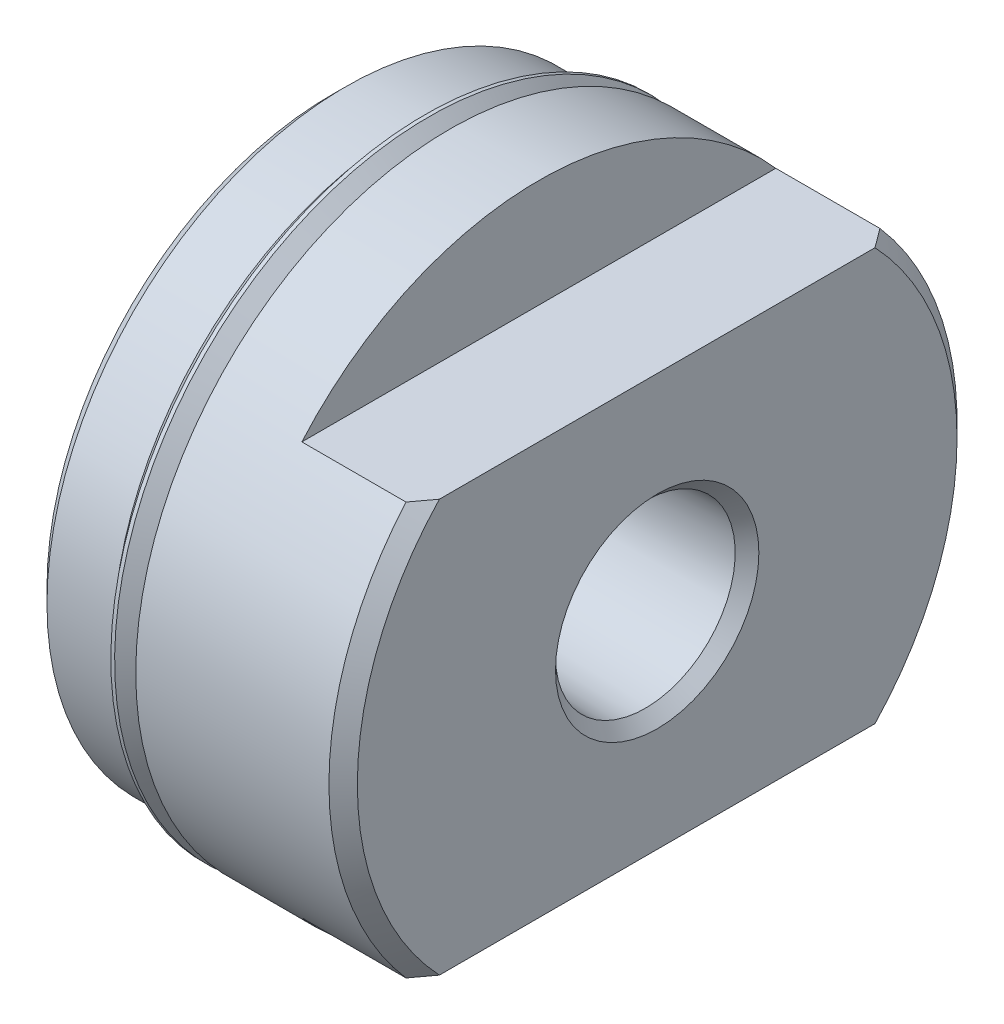
SolidWorks part; units mm, degrees
ref_plane "Front Plane" through (0, 0, 0) normal (0, 0, 1) x (1, 0, 0)
ref_plane "Top Plane" through (0, 0, 0) normal (0, 1, 0) x (1, 0, 0)
ref_plane "Right Plane" through (0, 0, 0) normal (1, 0, 0) x (0, 0, -1)
sketch "Sketch1" plane through (0, 0, 0) normal (0, 0, 1) x (1, 0, 0)
  line L0 (0, 0) -> (0, 15.2591)
  line L1 (0, 15.2591) -> (0.762, 16.021)
  line L2 (0.762, 16.021) -> (4.318, 16.021)
  line L3 (4.318, 16.021) -> (5.334, 15.0051)
  line L4 (5.334, 15.0051) -> (6.35, 15.0051)
  line L5 (6.35, 15.0051) -> (6.35, 16.8466)
  line L6 (6.35, 16.8466) -> (16.7132, 16.8466)
  line L7 (16.7132, 16.8466) -> (17.4752, 16.0846)
  line L8 (17.4752, 16.0846) -> (17.4752, 0)
  line L9 (17.4752, 0) -> (0, 0)
  line L10 (17.4752, 0) -> (0, 0) construction
revolve "Revolve1" add sketch "Sketch1" angle 360 about L10 reverse direction yes
sketch "Sketch2" plane through (0, 0, 0) normal (0, 0, 1) x (1, 0, 0)
  line L0 (0, 0) -> (0, 4.3688)
  line L1 (0, 4.3688) -> (2.3989, 4.3688)
  line L2 (2.3989, 4.3688) -> (16.8402, 4.8197)
  line L3 (16.8402, 4.8197) -> (17.4752, 5.4547)
  line L4 (17.4752, 5.4547) -> (17.4752, 0)
  line L5 (17.4752, 0) -> (0, 0)
  line L6 (17.4752, 0) -> (0, 0) construction
revolve "Cut-Revolve1" cut sketch "Sketch2" angle 360 about L6 reverse direction yes
cosmetic thread "Cosmetic Thread1" parameters "D1"=6.9342, "D2"=10.287
ref_plane "Plane1" through (17.4752, 0, 0) normal (1, 0, 0) x (0, 0, -1)
sketch "Sketch3" plane through (17.4752, 0, 0) normal (1, 0, 0) x (0, 0, -1)
  line L0 (-67.3862, 33.6931) -> (-67.3862, -33.6931)
  line L1 (-67.3862, -33.6931) -> (67.3862, -33.6931)
  line L2 (67.3862, -33.6931) -> (67.3862, 33.6931)
  line L3 (67.3862, 33.6931) -> (-67.3862, 33.6931)
  line L4 (-33.6931, 11.0554) -> (-33.6931, -11.0554)
  line L5 (-33.6931, -11.0554) -> (33.6931, -11.0554)
  line L6 (33.6931, -11.0554) -> (33.6931, 11.0554)
  line L7 (33.6931, 11.0554) -> (-33.6931, 11.0554)
extrude "Cut-Extrude1" cut sketch "Sketch3" against normal blind 6.35
sketch "Sketch4" plane through (0, 0, 0) normal (0, 0, 1) x (1, 0, 0)
  line L0 (0, 0) -> (0, 11.1125)
  line L1 (0, 11.1125) -> (7.9248, 11.1125)
  line L2 (7.9248, 11.1125) -> (7.9248, 0)
  line L3 (7.9248, 0) -> (0, 0)
  line L4 (7.9248, 0) -> (0, 0) construction
revolve "Cut-Revolve2" cut sketch "Sketch4" angle 360 about L4 reverse direction yes
ref_plane "Plane2" through (25.4, 0, 0) normal (1, 0, 0) x (0, 0, -1)
ref_plane "Plane3" through (0, 0, 0) normal (0, 0.9998, 0.0175) x (1, 0, 0)
ref_plane "Plane4" through (15.875, 0, 0) normal (1, 0, 0) x (0, 0, -1)
ref_plane "Plane5" through (5.334, 0, 0) normal (1, 0, 0) x (0, 0, -1)
sketch "Sketch5" plane through (0, 0, 0) normal (0, 0, 1) x (1, 0, 0)
  line L0 (5.0135, 16.7624) -> (6.2166, 15.5593)
  line L1 (6.2166, 15.3797) -> (5.842, 15.0051)
  line L2 (5.842, 15.0051) -> (5.334, 15.0051)
  line L3 (5.334, 15.0051) -> (5.334, 14.7511)
  line L4 (5.334, 14.7511) -> (6.35, 14.7511)
  line L5 (6.35, 14.7511) -> (6.35, 15.7133)
  line L6 (6.35, 15.7133) -> (5.2167, 16.8466)
  line L7 (5.2167, 16.8466) -> (5.0135, 16.8466)
  line L8 (5.0135, 16.8466) -> (5.0135, 16.7624)
  line L9 (6.35, 0) -> (5.334, 0) construction
  arc A0 (6.2166, 15.5593) -> (6.2166, 15.3797) centre (6.1268, 15.4695) cw
revolve "Revolve2" add sketch "Sketch5" angle 360 about L9 reverse direction yes
ref_plane "Plane6" through (17.6022, 0, 0) normal (1, 0, 0) x (0, 0, -1)
ref_plane "Plane7" through (0, 0, 0) normal (1, 0, 0) x (0, 0, -1)
ref_plane "Plane8" through (11.1252, 0, 0) normal (1, 0, 0) x (0, 0, -1)
ref_plane "Plane9" through (17.4752, 0, 0) normal (1, 0, 0) x (0, 0, -1)
ref_plane "Plane10" through (0, 0, 0) normal (0, 0, 1) x (1, 0, 0)
ref_plane "Plane11" through (0, 0, 0) normal (0, 1, 0) x (1, 0, 0)
ref_plane "Plane12" through (0, 0, 0) normal (0, 1, 0) x (1, 0, 0)
ref_plane "Plane13" through (25.4, 0, 0) normal (1, 0, 0) x (0, 0, -1)
ref_plane "cut1 XY" through (17.4752, 0, 0) normal (1, 0, 0) x (0, 0, -1)
ref_plane "cut1 XZ" through (0, 11.0554, 0) normal (0, -1, 0) x (-1, 0, 0)
ref_plane "cut1 YZ" through (0, 0, 0) normal (0, 0, -1) x (-1, 0, 0)
ref_axis "cut1 X" through (17.4752, 11.0554, 80.9) along (0, 0, -1)
ref_axis "cut1 Y" through (17.4752, -50, 0) along (0, 1, 0)
ref_axis "cut1 Z" through (80.9, 11.0554, 0) along (-1, 0, 0)
sketch3d "cut1"
  point P0 (17.4752, 11.0554, 0)
ref_plane "cut2 XY" through (17.4752, 0, 0) normal (1, 0, 0) x (0, 0, -1)
ref_plane "cut2 XZ" through (0, -11.0554, 0) normal (0, -1, 0) x (-1, 0, 0)
ref_plane "cut2 YZ" through (0, 0, 0) normal (0, 0, -1) x (-1, 0, 0)
ref_axis "cut2 X" through (17.4752, -11.0554, 80.9) along (0, 0, -1)
ref_axis "cut2 Y" through (17.4752, -50, 0) along (0, 1, 0)
ref_axis "cut2 Z" through (80.9, -11.0554, 0) along (-1, 0, 0)
sketch3d "cut2"
  point P0 (17.4752, -11.0554, 0)
ref_plane "cutf1 XY" through (0, 0, 0) normal (0, 0, 1) x (1, 0, 0)
ref_plane "cutf1 XZ" through (0, 0, 0) normal (0, -1, 0) x (-1, 0, 0)
ref_plane "cutf1 YZ" through (17.4752, 0, 0) normal (1, 0, 0) x (0, 0, -1)
ref_axis "cutf1 X" through (-80.9, 0, 0) along (1, 0, 0)
ref_axis "cutf1 Y" through (17.4752, -50, 0) along (0, 1, 0)
ref_axis "cutf1 Z" through (17.4752, 0, 80.9) along (0, 0, -1)
sketch3d "cutf1"
  point P0 (17.4752, 0, 0)
ref_plane "cutf2 XY" through (0, 0, 0) normal (0, 0, 1) x (1, 0, 0)
ref_plane "cutf2 XZ" through (0, 0, 0) normal (0, -1, 0) x (-1, 0, 0)
ref_plane "cutf2 YZ" through (11.1252, 0, 0) normal (1, 0, 0) x (0, 0, -1)
ref_axis "cutf2 X" through (-80.9, 0, 0) along (1, 0, 0)
ref_axis "cutf2 Y" through (11.1252, -50, 0) along (0, 1, 0)
ref_axis "cutf2 Z" through (11.1252, 0, 80.9) along (0, 0, -1)
sketch3d "cutf2"
  point P0 (11.1252, 0, 0)
ref_plane "lovra XY" through (17.4752, 0, 0) normal (1, 0, 0) x (0, 0, -1)
ref_plane "lovra XZ" through (0, 0, 0) normal (0, 0, -1) x (-1, 0, 0)
ref_plane "lovra YZ" through (0, 0, 0) normal (0, 1, 0) x (1, 0, 0)
ref_axis "lovra X" through (17.4752, -50, 0) along (0, 1, 0)
ref_axis "lovra Y" through (17.4752, 0, -80.9) along (0, 0, 1)
ref_axis "lovra Z" through (80.9, 0, 0) along (-1, 0, 0)
sketch3d "lovra"
  point P0 (17.4752, 0, 0)
ref_plane "lovra1 XY" through (11.1252, 0, 0) normal (1, 0, 0) x (0, 0, -1)
ref_plane "lovra1 XZ" through (0, 0, 0) normal (0, -1, 0) x (-1, 0, 0)
ref_plane "lovra1 YZ" through (0, 0, 0) normal (0, 0, -1) x (-1, 0, 0)
ref_axis "lovra1 X" through (11.1252, 0, 80.9) along (0, 0, -1)
ref_axis "lovra1 Y" through (11.1252, -50, 0) along (0, 1, 0)
ref_axis "lovra1 Z" through (80.9, 0, 0) along (-1, 0, 0)
sketch3d "lovra1"
  point P0 (11.1252, 0, 0)
ref_plane "lovra2 XY" through (11.1252, 0, 0) normal (1, 0, 0) x (0, 0, -1)
ref_plane "lovra2 XZ" through (0, 11.0554, 0) normal (0, -1, 0) x (-1, 0, 0)
ref_plane "lovra2 YZ" through (0, 0, 0) normal (0, 0, -1) x (-1, 0, 0)
ref_axis "lovra2 X" through (11.1252, 11.0554, 80.9) along (0, 0, -1)
ref_axis "lovra2 Y" through (11.1252, -50, 0) along (0, 1, 0)
ref_axis "lovra2 Z" through (80.9, 11.0554, 0) along (-1, 0, 0)
sketch3d "lovra2"
  point P0 (11.1252, 11.0554, 0)
ref_plane "lovra21 XY" through (0, 0, 0) normal (1, 0, 0) x (0, 0, -1)
ref_plane "lovra21 XZ" through (0, 0, 0) normal (0, -1, 0) x (-1, 0, 0)
ref_plane "lovra21 YZ" through (0, 0, 5.2705) normal (0, 0, -1) x (-1, 0, 0)
ref_axis "lovra21 X" through (0, 0, 80.9) along (0, 0, -1)
ref_axis "lovra21 Y" through (0, -50, 5.2705) along (0, 1, 0)
ref_axis "lovra21 Z" through (80.9, 0, 5.2705) along (-1, 0, 0)
sketch3d "lovra21"
  point P0 (0, 0, 5.2705)
ref_plane "lovra22 XY" through (0, 0, 0) normal (1, 0, 0) x (0, 0, -1)
ref_plane "lovra22 XZ" through (0, 0, 0) normal (0, -1, 0) x (-1, 0, 0)
ref_plane "lovra22 YZ" through (0, 0, -5.2705) normal (0, 0, -1) x (-1, 0, 0)
ref_axis "lovra22 X" through (0, 0, 80.9) along (0, 0, -1)
ref_axis "lovra22 Y" through (0, -50, -5.2705) along (0, 1, 0)
ref_axis "lovra22 Z" through (80.9, 0, -5.2705) along (-1, 0, 0)
sketch3d "lovra22"
  point P0 (0, 0, -5.2705)
ref_plane "lovra3 XY" through (11.1252, 0, 0) normal (1, 0, 0) x (0, 0, -1)
ref_plane "lovra3 XZ" through (0, -11.0554, 0) normal (0, -1, 0) x (-1, 0, 0)
ref_plane "lovra3 YZ" through (0, 0, 0) normal (0, 0, -1) x (-1, 0, 0)
ref_axis "lovra3 X" through (11.1252, -11.0554, 80.9) along (0, 0, -1)
ref_axis "lovra3 Y" through (11.1252, -50, 0) along (0, 1, 0)
ref_axis "lovra3 Z" through (80.9, -11.0554, 0) along (-1, 0, 0)
sketch3d "lovra3"
  point P0 (11.1252, -11.0554, 0)
ref_plane "olen XY" through (17.4752, 0, 0) normal (1, 0, 0) x (0, 0, -1)
ref_plane "olen XZ" through (0, 0, 0) normal (0, -1, 0) x (-1, 0, 0)
ref_plane "olen YZ" through (0, 0, 0) normal (0, 0, -1) x (-1, 0, 0)
ref_axis "olen X" through (17.4752, 0, 80.9) along (0, 0, -1)
ref_axis "olen Y" through (17.4752, -50, 0) along (0, 1, 0)
ref_axis "olen Z" through (80.9, 0, 0) along (-1, 0, 0)
sketch3d "olen"
  point P0 (17.4752, 0, 0)
ref_plane "to_mounting_bracket XY" through (25.4, 0, 0) normal (1, 0, 0) x (0, 0, -1)
ref_plane "to_mounting_bracket XZ" through (0, 0, 0) normal (0, -1, 0) x (-1, 0, 0)
ref_plane "to_mounting_bracket YZ" through (0, 0, 0) normal (0, 0, -1) x (-1, 0, 0)
ref_axis "to_mounting_bracket X" through (25.4, 0, 80.9) along (0, 0, -1)
ref_axis "to_mounting_bracket Y" through (25.4, -50, 0) along (0, 1, 0)
ref_axis "to_mounting_bracket Z" through (80.9, 0, 0) along (-1, 0, 0)
sketch3d "to_mounting_bracket"
  point P0 (25.4, 0, 0)
ref_plane "to_nut XY" through (0, 0, 0) normal (1, 0, 0) x (0, 0, -1)
ref_plane "to_nut XZ" through (0, 0, 0) normal (0, -1, 0) x (-1, 0, 0)
ref_plane "to_nut YZ" through (0, 0, 0) normal (0, 0, -1) x (-1, 0, 0)
ref_axis "to_nut X" through (0, 0, 80.9) along (0, 0, -1)
ref_axis "to_nut Y" through (0, -50, 0) along (0, 1, 0)
ref_axis "to_nut Z" through (80.9, 0, 0) along (-1, 0, 0)
sketch3d "to_nut"
  point P0 (0, 0, 0)
ref_plane "to_pin XY" through (0, 0, 0) normal (0, 0, 1) x (1, 0, 0)
ref_plane "to_pin XZ" through (0, 0, 0) normal (0, -1, 0) x (-1, 0, 0)
ref_plane "to_pin YZ" through (35.7124, 0, 0) normal (1, 0, 0) x (0, 0, -1)
ref_axis "to_pin X" through (-80.9, 0, 0) along (1, 0, 0)
ref_axis "to_pin Y" through (35.7124, -50, 0) along (0, 1, 0)
ref_axis "to_pin Z" through (35.7124, 0, 80.9) along (0, 0, -1)
sketch3d "to_pin"
  point P0 (35.7124, 0, 0)
ref_plane "to_screw XY" through (0, 0, 0) normal (0, 1, 0) x (1, 0, 0)
ref_plane "to_screw XZ" through (0, 0, 0) normal (0, 0, 1) x (1, 0, 0)
ref_plane "to_screw YZ" through (15.875, 0, 0) normal (1, 0, 0) x (0, 0, -1)
ref_axis "to_screw X" through (-80.9, 0, 0) along (1, 0, 0)
ref_axis "to_screw Y" through (15.875, 0, 50) along (0, 0, -1)
ref_axis "to_screw Z" through (15.875, 50, 0) along (0, -1, 0)
sketch3d "to_screw"
  point P0 (15.875, 0, 0)
ref_plane "to_tube XY" through (5.334, 0, 0) normal (1, 0, 0) x (0, 0, -1)
ref_plane "to_tube XZ" through (0, 0, 0) normal (0, -1, 0) x (-1, 0, 0)
ref_plane "to_tube YZ" through (0, 0, 0) normal (0, 0, -1) x (-1, 0, 0)
ref_axis "to_tube X" through (5.334, 0, 80.9) along (0, 0, -1)
ref_axis "to_tube Y" through (5.334, -50, 0) along (0, 1, 0)
ref_axis "to_tube Z" through (80.9, 0, 0) along (-1, 0, 0)
sketch3d "to_tube"
  point P0 (5.334, 0, 0)
